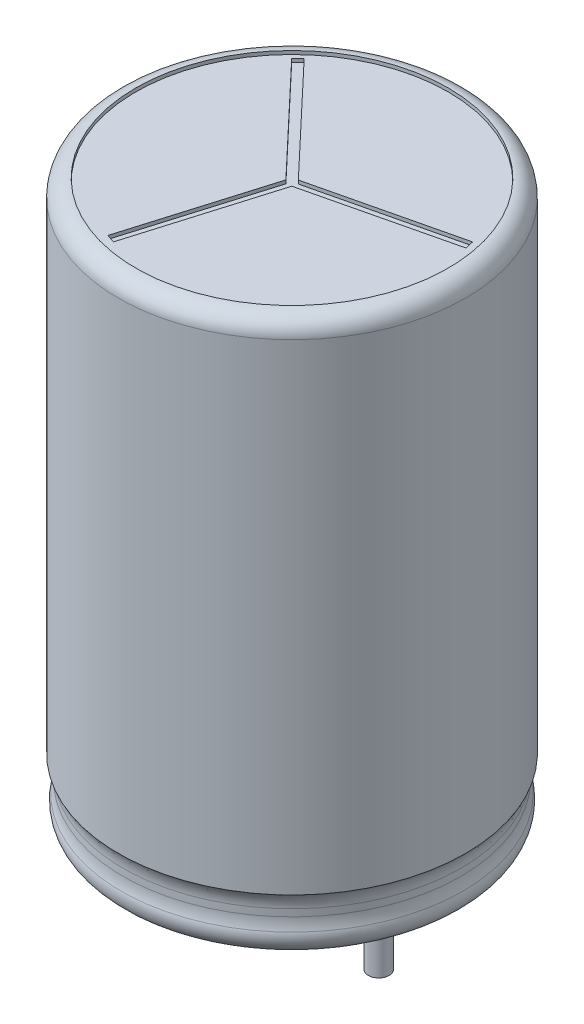
SolidWorks part; units mm, degrees
ref_plane "Front Plane" through (0, 0, 0) normal (0, 0, 1) x (1, 0, 0)
ref_plane "Top Plane" through (0, 0, 0) normal (0, 1, 0) x (1, 0, 0)
ref_plane "Right Plane" through (0, 0, 0) normal (1, 0, 0) x (0, 0, -1)
sketch "Sketch1" plane through (0, 0, 0) normal (0, 0, 1) x (1, 0, 0)
  line L0 (5, 16) -> (0, 16)
  line L1 (0, 16) -> (0, 0)
  line L2 (0, 0) -> (4.8272, 0)
  line L3 (4.8617, 1.0001) -> (4.8617, 1.2029)
  line L4 (5, 1.6447) -> (5, 16)
  line L5 (0, 16) -> (0, 0) construction
  arc A0 (4.8272, 0) -> (4.9619, 0.5462) centre (4.5545, 0.357) ccw
  arc A1 (4.9619, 0.5462) -> (4.8617, 1.0001) centre (5.939, 1.0001) cw
  arc A2 (4.8617, 1.2029) -> (4.9985, 1.64) centre (5.628, 1.2029) cw
  arc A3 (4.9985, 1.64) -> (5, 1.6447) centre (4.9916, 1.6447) ccw
  point P14 (0, 0)
  point P15 (4.798, -1.4348)
  point P16 (4.8982, -1.8887)
  point P17 (0, 0)
  dimension "D1" = 16
  dimension "D2" = 5
revolve "Revolve1" add sketch "Sketch1" angle 360 about L5 reverse direction yes
sketch "Sketch2" plane through (0, 16, 0) normal (0, 1, 0) x (-1, 0, 0)
  circle A0 centre (0, 0) radius 4.5
  dimension "D1" = 9
extrude "Cut-Extrude1" cut sketch "Sketch2" against normal blind 0.1
sketch "Sketch3" plane through (0, 15.9, 0) normal (0, 1, 0) x (-1, 0, 0)
  line L0 (2.906, -3.2561) -> (3.0905, -3.0815)
  line L1 (3.0905, -3.0815) -> (0.1426, 0.034)
  line L2 (0.1426, 0.034) -> (1.3206, 3.9896)
  line L3 (1.3206, 3.9896) -> (1.0772, 4.0621)
  line L4 (1.0772, 4.0621) -> (-0.1008, 0.1065)
  line L5 (-0.1008, 0.1065) -> (-4.1556, -0.8607)
  line L6 (-4.1556, -0.8607) -> (-4.0967, -1.1077)
  line L7 (-4.0967, -1.1077) -> (-0.0419, -0.1405)
  line L8 (-0.0419, -0.1405) -> (2.906, -3.2561)
extrude "Cut-Extrude2" cut sketch "Sketch3" against normal blind 0.1
ref_plane "Plane1" through (0, 0, 0) normal (0, 0, -1) x (-1, 0, 0)
sketch "Sketch4" plane through (0, 0, 0) normal (0, 0, -1) x (-1, 0, 0)
  line L0 (-2.8, -2.5) -> (-2.5, -2.5)
  line L1 (-2.5, -2.5) -> (-2.5, 0)
  line L2 (-2.5, 0) -> (-2.8, 0)
  line L3 (-2.8, 0) -> (-2.8, -2.5)
  line L4 (-2.5, -2.5) -> (-2.5, 0) construction
  dimension "D1" = 2.5
  dimension "D2" = 0.3
revolve "Revolve2" add sketch "Sketch4" angle 360 about L4 other way angle 360 reverse direction yes
fillet "Fillet1" radius 0.5 2 edges at (5, 16, 0) (4.8272, 0, 0) tangent propagation no
mirror "Simetría3" about plane through (0, 0, 0) normal (1, 0, 0) of "Revolve2"
